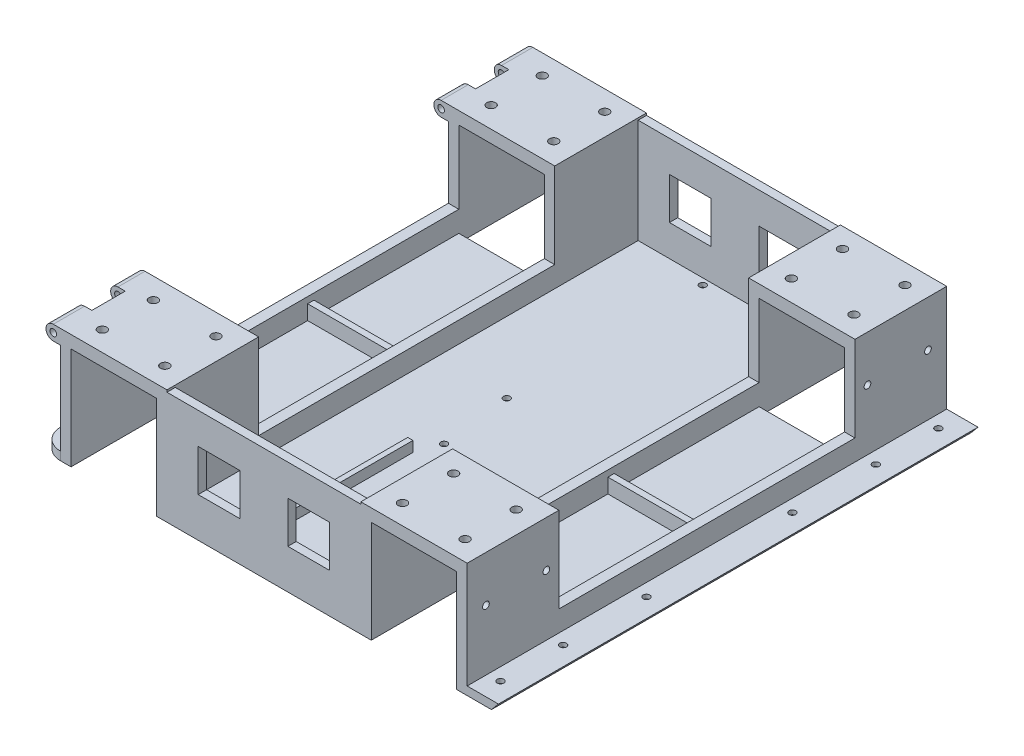
SolidWorks part; units mm, degrees
ref_plane "前视基准面" through (0, 0, 0) normal (0, 0, 1) x (1, 0, 0)
ref_plane "上视基准面" through (0, 0, 0) normal (0, 1, 0) x (1, 0, 0)
ref_plane "右视基准面" through (0, 0, 0) normal (1, 0, 0) x (0, 0, -1)
other "Configuration Table"
sketch "草图1" plane through (0, 0, 0) normal (0, 1, 0) x (1, 0, 0)
  line L0 (-110, 0) -> (110, 0) construction
  line L1 (110, -115) -> (-110, -115)
  line L2 (110, -115) -> (110, 115)
  line L3 (110, 115) -> (-110, 115)
  line L4 (-110, -115) -> (-110, 115)
  line L5 (110, -115) -> (-110, 115) construction
  line L6 (110, 115) -> (-110, -115) construction
  line L7 (0, 115) -> (0, -115) construction
  point P0 (0, 0)
  dimension "D1" = 220
  dimension "D2" = 230
extrude "凸台-拉伸1" add sketch "草图1" along normal blind 4
sketch "草图2" plane through (0, 4, 0) normal (0, 1, 0) x (1, 0, 0)
  line L1 (-95, 71) -> (-100, 71)
  line L2 (49, 115) -> (90, 115)
  line L3 (49, 115) -> (49, 71)
  line L4 (49, 71) -> (90, 71)
  line L5 (-110, 115) -> (-110, -115)
  line L6 (-110, -115) -> (110, -115)
  line L7 (110, -115) -> (110, 115)
  line L8 (110, 115) -> (-110, 115)
  line L9 (-110, 115) -> (-110, -115)
  line L10 (-110, -115) -> (110, -115)
  line L11 (110, -115) -> (110, 115)
  line L12 (110, 115) -> (-110, 115)
  line L13 (90, 115) -> (90, 71)
  line L14 (-95, 115) -> (-54, 115)
  line L15 (-95, 115) -> (-95, 71)
  line L16 (-95, 71) -> (-54, 71)
  line L17 (-54, 115) -> (-54, 71)
  line L18 (-95, -115) -> (-54, -115)
  line L19 (-95, -115) -> (-95, -71)
  line L20 (-95, -71) -> (-54, -71)
  line L21 (-54, -115) -> (-54, -71)
  line L22 (90, -115) -> (49, -115)
  line L23 (90, -115) -> (90, -71)
  line L24 (90, -71) -> (49, -71)
  line L25 (49, -115) -> (49, -71)
  line L26 (90, -115) -> (95, -115)
  line L27 (90, -115) -> (90, -71)
  line L28 (90, -71) -> (95, -71)
  line L29 (95, -115) -> (95, -71)
  line L30 (49, -115) -> (44, -115)
  line L31 (49, -115) -> (49, -71)
  line L32 (49, -71) -> (44, -71)
  line L33 (44, -115) -> (44, -71)
  line L34 (90, 71) -> (95, 71)
  line L35 (90, 71) -> (90, 115)
  line L36 (90, 115) -> (95, 115)
  line L37 (95, 71) -> (95, 115)
  line L38 (49, 71) -> (44, 71)
  line L39 (49, 71) -> (49, 115)
  line L40 (49, 115) -> (44, 115)
  line L41 (44, 71) -> (44, 115)
  line L42 (-54, 71) -> (-49, 71)
  line L43 (-54, 71) -> (-54, 115)
  line L44 (-54, 115) -> (-49, 115)
  line L45 (-49, 71) -> (-49, 115)
  line L46 (-54, -71) -> (-49, -71)
  line L47 (-54, -71) -> (-54, -115)
  line L48 (-54, -115) -> (-49, -115)
  line L49 (-49, -71) -> (-49, -115)
  line L50 (-95, 71) -> (-95, 115)
  line L51 (-95, 115) -> (-100, 115)
  line L52 (-100, 71) -> (-100, 115)
  line L53 (-95, -71) -> (-100, -71)
  line L54 (-95, -71) -> (-95, -115)
  line L55 (-95, -115) -> (-100, -115)
  line L56 (-100, -71) -> (-100, -115)
  line M26 (-110, -115) -> (110, -115)
  line M28 (110, 115) -> (-110, 115)
  dimension "D2" = 44
  dimension "D3" = 41
  dimension "D4" = 44
  dimension "D5" = 41
  dimension "D6" = 41
  dimension "D7" = 44
  dimension "D8" = 44
  dimension "D9" = 41
  dimension "D10" = 15
  dimension "D11" = 15
  dimension "D12" = 20
  dimension "D13" = 20
  dimension "D14" = 5
  dimension "D15" = 5
  dimension "D16" = 5
  dimension "D17" = 5
  dimension "D18" = 5
  dimension "D19" = 5
  dimension "D20" = 5
  dimension "D21" = 5
  dimension "D1" = 0
extrude "凸台-拉伸2" add sketch "草图2" along normal blind 45 contours L53 L56 L10 L19 | L49 L46 L21 M26 | L33 L10 L25 L32 | L29 L28 L23 M26 | L34 L37 L12 L13 | L41 L38 L3 M28 | L42 L45 L17 M28 | L52 L1 L15 M28 region at (-97.5, 4, -93) region at (-51.5, 4, -93) region at (46.5, 4, -93) region at (-97.5, 4, 93) region at (92.5, 4, -93) region at (-51.5, 4, 93) region at (46.5, 4, 93) region at (92.5, 4, 93)
extrude "切除-拉伸1" cut sketch "草图2<3>" against normal up to surface (4 mm away) contours L10 L21 L20 L19 | L25 L10 L23 L24 | L17 L12 L15 L16 | L13 L3 L4 M28 region at (-74.5, 4, -93) region at (69.5, 4, -93) region at (-74.5, 4, 93) region at (69.5, 4, 93) up to face at (0, 0, 0)
sketch "草图2<3>" plane through (0, 4, 0) normal (0, 1, 0) x (1, 0, 0) same geometry as "草图2"
ref_plane "基准面1" through (0, 49, 0) normal (0, 1, 0) x (1, 0, 0)
sketch "草图3" plane through (0, 49, 0) normal (0, 1, 0) x (1, 0, 0)
  line L0 (-100, -115) -> (59, -115)
  line L1 (-168, -115) -> (95, -115)
  line L2 (-100, 115) -> (59, 115)
  line L3 (-170, 115) -> (95, 115)
  line L31 (95, -115) -> (110, -115)
  line L32 (110, -115) -> (110, 115)
  line L33 (110, 115) -> (95, 115)
  line L35 (49, -71) -> (90, -71)
  line L36 (49, -71) -> (90, -71)
  line L37 (90, -71) -> (95, -71)
  line L38 (90, -71) -> (95, -71)
  line L39 (95, -71) -> (95, -115)
  line L40 (95, -71) -> (95, -115)
  line L41 (95, 115) -> (95, 71)
  line L42 (95, 115) -> (95, 71)
  line L43 (-95, 71) -> (-100, 71)
  line L44 (-100, 71) -> (-100, 115)
  line L45 (95, 71) -> (90, 71)
  line L46 (-110, 115) -> (-110, -115)
  line L47 (95, 71) -> (90, 71)
  line L48 (-100, -115) -> (-100, -71)
  line L49 (-100, -71) -> (-95, -71)
  line L50 (90, 71) -> (49, 71)
  line L51 (90, 71) -> (49, 71)
  line L52 (49, 71) -> (44, 71)
  line L53 (49, 71) -> (44, 71)
  line L54 (44, 71) -> (44, 115)
  line L55 (44, 71) -> (44, 115)
  line L59 (95, -115) -> (110, -115)
  line L60 (110, -115) -> (110, 115)
  line L61 (110, 115) -> (95, 115)
  line L71 (-95, 71) -> (-100, 71)
  line L72 (-100, 71) -> (-100, 115)
  line L74 (-110, 115) -> (-110, -115)
  line L76 (-100, -115) -> (-100, -71)
  line L77 (-100, -71) -> (-95, -71)
  line L84 (44, 115) -> (-49, 115)
  line L85 (44, 115) -> (-49, 115)
  line L86 (-49, 115) -> (-49, 71)
  line L87 (-49, 115) -> (-49, 71)
  line L88 (-49, 71) -> (-54, 71)
  line L89 (-49, 71) -> (-54, 71)
  line L90 (-54, 71) -> (-95, 71)
  line L91 (-54, 71) -> (-95, 71)
  line L92 (-100, 115) -> (-110, 115)
  line L93 (-100, 115) -> (-110, 115)
  line L94 (-110, -115) -> (-100, -115)
  line L95 (-110, -115) -> (-100, -115)
  line L96 (-95, -71) -> (-54, -71)
  line L97 (-95, -71) -> (-54, -71)
  line L98 (-54, -71) -> (-49, -71)
  line L99 (-54, -71) -> (-49, -71)
  line L100 (-49, -71) -> (-49, -115)
  line L101 (-49, -71) -> (-49, -115)
  line L102 (-49, -115) -> (44, -115)
  line L103 (-49, -115) -> (44, -115)
  line L104 (44, -115) -> (44, -71)
  line L105 (44, -115) -> (44, -71)
  line L106 (44, -71) -> (49, -71)
  line L107 (44, -71) -> (49, -71)
  dimension "D1" = 0
extrude "凸台-拉伸3" add sketch "草图3" along normal blind 6 contours L101 L99 L97 L77 L76 L0 | L72 L71 L91 L89 L87 L2 | L55 L53 L51 L47 L42 L3 | L107 L105 L1 L40 L38 L36 region at (-74.5, 49, 93) region at (69.5, 49, 93) region at (-74.5, 49, -93) region at (69.5, 49, -93)
sketch "草图4" plane through (0, 49, 0) normal (0, -1, 0) x (1, 0, 0)
  line L0 (69.5, -115) -> (69.5, -71) construction
  line L1 (-74.5, -115) -> (-74.5, -71) construction
  line L2 (110, 115) -> (110, -115) construction
  line L3 (110, 115) -> (110, -115) construction
  line L4 (49, -115) -> (90, -115)
  line L5 (90, -115) -> (90, -71)
  line L6 (90, -71) -> (49, -71)
  line L7 (49, -71) -> (49, -115)
  line L8 (49, -115) -> (90, -115)
  line L9 (90, -115) -> (90, -71)
  line L10 (90, -71) -> (49, -71)
  line L11 (49, -71) -> (49, -115)
  line L12 (-110, -115) -> (-110, 115) construction
  line L13 (-95, -71) -> (-95, -115)
  line L14 (-95, -115) -> (-54, -115)
  line L15 (-54, -115) -> (-54, -71)
  line L16 (-54, -71) -> (-95, -71)
  line L17 (-95, -71) -> (-95, -115)
  line L18 (-95, -115) -> (-54, -115)
  line L19 (-54, -115) -> (-54, -71)
  line L20 (-54, -71) -> (-95, -71)
  line L21 (-110, -115) -> (-110, 115) construction
  line L22 (110, 0) -> (-110, 0) construction
  line L23 (-74.5, 115) -> (-74.5, 71) construction
  line L24 (-54, 71) -> (-95, 71)
  line L25 (-54, 115) -> (-54, 71)
  line L26 (-95, 115) -> (-54, 115)
  line L27 (-95, 71) -> (-95, 115)
  line L28 (69.5, 115) -> (69.5, 71) construction
  line L29 (49, 71) -> (49, 115)
  line L30 (90, 71) -> (49, 71)
  line L31 (90, 115) -> (90, 71)
  line L32 (49, 115) -> (90, 115)
  circle A0 centre (84.5, -105.5) radius 2.1
  circle A1 centre (54.5, -105.5) radius 2.1
  circle A2 centre (54.5, -81) radius 2.1
  circle A3 centre (84.5, -81) radius 2.1
  circle A4 centre (-59.5, -105.5) radius 2.1
  circle A5 centre (-89.5, -105.5) radius 2.1
  circle A6 centre (-59.5, -81) radius 2.1
  circle A7 centre (-89.5, -81) radius 2.1
  circle A8 centre (-89.5, 81) radius 2.1
  circle A9 centre (-59.5, 81) radius 2.1
  circle A10 centre (-89.5, 105.5) radius 2.1
  circle A11 centre (-59.5, 105.5) radius 2.1
  circle A12 centre (84.5, 81) radius 2.1
  circle A13 centre (54.5, 81) radius 2.1
  circle A14 centre (54.5, 105.5) radius 2.1
  circle A15 centre (84.5, 105.5) radius 2.1
  dimension "D4" = 0
  dimension "D5" = 4.2
  dimension "D6" = 4.2
  dimension "D7" = 4.2
  dimension "D9" = 4.2
  dimension "D10" = 4.2
  dimension "D2" = 24.5
  dimension "D3" = 30
  dimension "D8" = 9.5
  dimension "D11" = 30
  dimension "D12" = 24.5
  dimension "D13" = 9.5
  dimension "D1" = 0
extrude "切除-拉伸2" cut sketch "草图4" against normal up to surface (6 mm away) contours A15 | A12 | A14 | A13 | A11 | A9 | A10 | A8 | A7 | A5 | A4 | A6 | A2 | A1 | A0 | A3 region at (84.5, 49, -105.5) region at (54.5, 49, -105.5) region at (54.5, 49, -81) region at (84.5, 49, -81) region at (-59.5, 49, -105.5) region at (-89.5, 49, -105.5) region at (-59.5, 49, -81) region at (-89.5, 49, -81) region at (-89.5, 49, 81) region at (-59.5, 49, 81) region at (-89.5, 49, 105.5) region at (-59.5, 49, 105.5) region at (84.5, 49, 81) region at (54.5, 49, 81) region at (54.5, 49, 105.5) region at (84.5, 49, 105.5) up to face at (69.5, 55, -93)
sketch "草图10" plane through (0, 4, 0) normal (0, 1, 0) x (1, 0, 0)
  line L0 (44, -115) -> (44, -71) construction
  line L1 (-49, -115) -> (44, -115)
  line L2 (-49, -115) -> (-49, -111)
  line L3 (-49, -111) -> (44, -111)
  line L4 (44, -115) -> (44, -111)
  line L5 (44, 71) -> (44, 115) construction
  line L6 (-49, 115) -> (44, 115)
  line L7 (-49, 115) -> (-49, 111)
  line L8 (-49, 111) -> (44, 111)
  line L9 (44, 115) -> (44, 111)
  dimension "D1" = 4
  dimension "D2" = 4
extrude "凸台-拉伸8" add sketch "草图10" along normal blind 50
sketch "草图11" plane through (0, 4, 0) normal (0, 1, 0) x (1, 0, 0)
  line L0 (-95, -71) -> (-100, -71) construction
  line L1 (-49, 71) -> (-54, 71)
  line L2 (-49, 71) -> (-49, -71)
  line L3 (-49, -71) -> (-54, -71)
  line L4 (-54, 71) -> (-54, -71)
  line L5 (90, 71) -> (95, 71)
  line L6 (90, 71) -> (90, -71)
  line L7 (90, -71) -> (95, -71)
  line L8 (95, 71) -> (95, -71)
  line L9 (-95, 71) -> (-100, 71)
  line L10 (-95, 71) -> (-95, -71)
  line L11 (-95, -71) -> (-100, -71)
  line L12 (-100, 71) -> (-100, -71)
  line L14 (49, 71) -> (44, 71)
  line L15 (49, 71) -> (49, -71)
  line L16 (49, -71) -> (44, -71)
  line L17 (44, 71) -> (44, -71)
  dimension "D1" = 5
extrude "凸台-拉伸9" add sketch "草图11" along normal blind 10
sketch "草图13" plane through (0, 4, 0) normal (0, 1, 0) x (1, 0, 0)
  line L0 (-95, 0) -> (-51.7865, 0)
  line L1 (90, 0) -> (49, 0)
  line L2 (-51.7865, -1.5) -> (-95, -1.5)
  line L3 (-51.7865, -1.5) -> (-51.7865, 1.5)
  line L4 (-54, 71) -> (-95, 71)
  line L5 (-95, 71) -> (-95, -71)
  line L6 (-95, -71) -> (-54, -71)
  line L8 (-54, 71) -> (-95, 71)
  line L10 (-95, -71) -> (-54, -71)
  line L12 (-51.7865, 1.5) -> (-95, 1.5)
  line L13 (-95, -1.5) -> (-95, 1.5)
  line L14 (-51.7865, -1.5) -> (-95, 1.5) construction
  line L15 (-51.7865, 1.5) -> (-95, -1.5) construction
  line L17 (49, -1.5) -> (90, -1.5)
  line L18 (49, -1.5) -> (49, 1.5)
  line L19 (-95, 71) -> (-95, -71)
  line L20 (-54, -71) -> (-54, 71)
  line L21 (-54, -71) -> (-54, 71)
  line L22 (90, 71) -> (49, 71)
  line L23 (49, 71) -> (49, -71)
  line L24 (49, -71) -> (90, -71)
  line L25 (90, -71) -> (90, 71)
  line L26 (90, 71) -> (49, 71)
  line L27 (49, 71) -> (49, -71)
  line L28 (49, -71) -> (90, -71)
  line L29 (90, -71) -> (90, 71)
  line L30 (49, 1.5) -> (90, 1.5)
  line L31 (90, -1.5) -> (90, 1.5)
  line L32 (49, -1.5) -> (90, 1.5) construction
  line L33 (49, 1.5) -> (90, -1.5) construction
  point P6 (-73.3932, 0)
  point P11 (69.5, 0)
  line M8 (-95, 71) -> (-95, -71)
  line M10 (-54, -71) -> (-54, 71)
  dimension "D2" = 3
  dimension "D4" = 3
  dimension "D1" = 0
  dimension "D3" = 0
extrude "凸台-拉伸11" add sketch "草图13" along normal blind 7 contours L2 L0 M10 M8 | L12 L19 L0 M10 | L30 L18 L1 L29 | L17 L29 L1 L18 region at (-74.5, 4, -0.75) region at (-74.5, 4, 0.75) region at (69.5, 4, 0.75) region at (69.5, 4, -0.75)
sketch "草图17" plane through (0, 4, 0) normal (0, 1, 0) x (1, 0, 0)
  line L0 (101, -115) -> (101, -71) construction
  line L1 (133.9214, 0) -> (95, 0) construction
  line L4 (110, 115) -> (95, 115)
  line L5 (95, 115) -> (95, -115)
  line L6 (95, -115) -> (110, -115)
  line L7 (110, -115) -> (110, 115)
  line L9 (95, 115) -> (95, -115)
  line L10 (95, -115) -> (110, -115)
  line L14 (110, -115) -> (110, 115)
  line L15 (110, 115) -> (95, 115)
  circle A2 centre (101, -35) radius 1.6
  circle A3 centre (101, -75) radius 1.6
  circle A4 centre (101, -105) radius 1.6
  circle A5 centre (101, 35) radius 1.6
  circle A6 centre (101, 75) radius 1.6
  circle A7 centre (101, 105) radius 1.6
  dimension "D3" = 35
  dimension "D4" = 3.2
  dimension "D5" = 3.2
  dimension "D6" = 3.2
  dimension "D2" = 6
  dimension "D7" = 75
  dimension "D8" = 105
  dimension "D1" = 0
extrude "切除-拉伸7" cut sketch "草图17" against normal up to surface (4 mm away) contours A4 | A3 | A2 | A5 | A6 | A7 region at (101, 4, 35) region at (101, 4, 75) region at (101, 4, 105) region at (101, 4, -35) region at (101, 4, -75) region at (101, 4, -105) up to face at (-2, 0, 0)
chamfer "倒角3" distance 4 angle 40 1 edges at (110, 0, 0) first distance on face at (110, 2, 0)
sketch "草图21" plane through (0, 0, -111) normal (0, 0, 1) x (1, 0, 0)
  line L1 (-34, 39) -> (-14, 39)
  line L2 (-34, 39) -> (-34, 19)
  line L3 (-34, 19) -> (-14, 19)
  line L4 (-49, 4) -> (44, 4)
  line L5 (44, 4) -> (44, 54)
  line L6 (44, 54) -> (-49, 54)
  line L7 (-49, 54) -> (-49, 4)
  line L8 (-49, 4) -> (44, 4)
  line L9 (44, 4) -> (44, 54)
  line L10 (44, 54) -> (-49, 54)
  line L11 (-49, 54) -> (-49, 4)
  line L12 (-14, 39) -> (-14, 19)
  line L13 (9, 39) -> (29, 39)
  line L14 (9, 39) -> (9, 19)
  line L15 (9, 19) -> (29, 19)
  line L16 (29, 39) -> (29, 19)
  dimension "D2" = 20
  dimension "D3" = 20
  dimension "D4" = 20
  dimension "D5" = 20
  dimension "D6" = 15
  dimension "D7" = 35
  dimension "D8" = 35
  dimension "D10" = 15
  dimension "D1" = 0
extrude "切除-拉伸11" cut sketch "草图21" against normal up to surface (4 mm away) and the other way through all contours L16 L13 L14 L15 | L12 L1 L2 L3 region at (-24, 29, -111) region at (19, 29, -111) up to face at (-2.1678, 27, -115)
sketch "草图23" plane through (0, 0, -71) normal (0, 0, 1) x (1, 0, 0)
  line L0 (-103.5, 55) -> (-100, 55)
  line L1 (-103.5, 48) -> (-100, 48)
  line L2 (-100, 48) -> (-100, 55)
  line L10 (-100, 55) -> (-100, 14)
  line L12 (-100, 55) -> (-100, 14)
  line L13 (-95, 49) -> (-54, 49)
  line L15 (-100, 14) -> (-95, 14)
  line L17 (-49, 55) -> (-100, 55)
  line L19 (-100, 14) -> (-95, 14)
  line L23 (-95, 49) -> (-54, 49)
  line L27 (-49, 55) -> (-100, 55)
  line L31 (-95, 14) -> (-95, 49)
  line L33 (-95, 14) -> (-95, 49)
  line L34 (-54, 49) -> (-54, 14)
  line L35 (-54, 49) -> (-54, 14)
  line L36 (-54, 14) -> (-49, 14)
  line L37 (-54, 14) -> (-49, 14)
  line L38 (-49, 14) -> (-49, 55)
  line L39 (-49, 14) -> (-49, 55)
  arc A0 (-103.5, 55) -> (-103.5, 48) centre (-103.5, 51.5) ccw
  circle A1 centre (-103.5, 51.5) radius 1.6
  line M19 (-100, 55) -> (-100, 14)
  dimension "D2" = 7
  dimension "D3" = 3.2
  dimension "D1" = 0
extrude "凸台-拉伸13" add sketch "草图23" against normal up to surface (44 mm away) contours L0 A0 L1 A1 M19 region at (-101.75, 54.901, -71) up to face at (-24, 29, -115)
extrude "切除-拉伸13" cut sketch "草图23<4>" against normal blind 16 from offset 13 contours L0 A0 L1 A1 M19 region at (-101.75, 54.901, -71) offset against normal yes
sketch "草图23<4>" plane through (0, 0, -71) normal (0, 0, 1) x (1, 0, 0) same geometry as "草图23"
extrude "凸台-拉伸14" add sketch "草图23<5>" along normal up to surface (186 mm away) from surface contours L0 A0 L1 A1 M19 region at (-101.75, 54.901, -71) up to face at (-24, 29, 115) starting at face at (-74.5, 33, 71)
sketch "草图23<5>" plane through (0, 0, -71) normal (0, 0, 1) x (1, 0, 0) same geometry as "草图23"
sketch "草图24" plane through (0, 4, 0) normal (0, 1, 0) x (1, 0, 0)
  line L1 (44, -111) -> (-14, -111)
  line L2 (44, -111) -> (44, -26)
  line L3 (44, -26) -> (-14, -26)
  line L4 (-49, -111) -> (44, -111)
  line L5 (44, -111) -> (44, 111)
  line L6 (44, 111) -> (-49, 111)
  line L7 (-49, 111) -> (-49, -111)
  line L8 (-49, -111) -> (44, -111)
  line L9 (44, -111) -> (44, 111)
  line L10 (44, 111) -> (-49, 111)
  line L11 (-49, 111) -> (-49, -111)
  line L12 (-14, -111) -> (-14, -26)
  line L13 (-15, -111) -> (-17.5, -111)
  line L14 (-15, -111) -> (-15, -31)
  line L15 (-15, -31) -> (-17.5, -31)
  line L16 (-17.5, -111) -> (-17.5, -31)
  dimension "D2" = 85
  dimension "D3" = 58
  dimension "D4" = 2.5
  dimension "D5" = 1
  dimension "D1" = 0
extrude "凸台-拉伸15" add sketch "草图24" along normal blind 5 contours L16 L8 L14 L15 region at (-16.25, 4, 71)
sketch "草图25" plane through (0, 4, 0) normal (0, 1, 0) x (1, 0, 0)
  line L8 (-17.5, -111) -> (-17.5, -31)
  line L9 (-17.5, -31) -> (-15, -31)
  line L10 (-15, -31) -> (-15, -111)
  line L11 (-15, -111) -> (44, -111)
  line L12 (44, -111) -> (44, 111)
  line L13 (44, 111) -> (-49, 111)
  line L14 (-49, 111) -> (-49, -111)
  line L15 (-49, -111) -> (-17.5, -111)
  line L16 (-17.5, -111) -> (-17.5, -31)
  line L17 (-17.5, -31) -> (-15, -31)
  line L18 (-15, -31) -> (-15, -111)
  line L19 (-15, -111) -> (44, -111)
  line L20 (44, -111) -> (44, 111)
  line L21 (44, 111) -> (-49, 111)
  line L22 (-49, 111) -> (-49, -111)
  line L23 (-49, -111) -> (-17.5, -111)
  circle A0 centre (40.9, -20) radius 1.6
  circle A1 centre (-11.1, -20) radius 1.6
  dimension "D2" = 3.2
  dimension "D3" = 3.2
  dimension "D1" = 52
  dimension "D5" = 91
  dimension "D6" = 91
  dimension "D7" = 3.1
  dimension "D4" = 0
extrude "切除-拉伸15" cut sketch "草图25" against normal up to surface (4 mm away) contours A0 | A1 region at (40.9, 4, 20) region at (-11.1, 4, 20) up to face at (101, 0, 106.6)
mirror "镜向6" about plane through (0, 0, 0) normal (0, 0, 1) of "切除-拉伸13"
fillet "圆角1" radius 10 2 edges at (-110, 2, 115) (-110, 2, -115)
sketch "草图26" plane through (0, 4, 0) normal (0, 1, 0) x (1, 0, 0)
  line L0 (13, 11) -> (13, 111) construction
  line L1 (44, 111) -> (-18, 111)
  line L2 (44, 111) -> (44, 11)
  line L3 (44, 11) -> (-18, 11)
  line L4 (-18, 111) -> (-18, 11)
  line L5 (-18, 61) -> (44, 61) construction
  line L8 (-17.5, -111) -> (-17.5, -31)
  line L9 (-17.5, -31) -> (-15, -31)
  line L10 (-15, -31) -> (-15, -111)
  line L11 (-15, -111) -> (44, -111)
  line L12 (44, -111) -> (44, 111)
  line L13 (44, 111) -> (-49, 111)
  line L14 (-49, 111) -> (-49, -111)
  line L15 (-49, -111) -> (-17.5, -111)
  line L16 (-17.5, -111) -> (-17.5, -31)
  line L17 (-17.5, -31) -> (-15, -31)
  line L18 (-15, -31) -> (-15, -111)
  line L19 (-15, -111) -> (44, -111)
  line L20 (44, -111) -> (44, 111)
  line L21 (44, 111) -> (-49, 111)
  line L22 (-49, 111) -> (-49, -111)
  line L23 (-49, -111) -> (-17.5, -111)
  circle A0 centre (41, 14) radius 1.6
  circle A1 centre (-15, 14) radius 1.6
  circle A2 centre (41, 108) radius 1.6
  circle A3 centre (-15, 108) radius 1.6
  dimension "D6" = 3.2
  dimension "D2" = 100
  dimension "D3" = 62
  dimension "D4" = 56
  dimension "D5" = 94
  dimension "D1" = 0
extrude "切除-拉伸16" cut sketch "草图26" against normal up to surface (4 mm away) contours A2 | A0 | A1 | A3 region at (41, 4, -14) region at (-15, 4, -14) region at (41, 4, -108) region at (-15, 4, -108) up to face at (40.9, 0, 21.6)
sketch "草图27" plane through (0, 0, 0) normal (0, -1, 0) x (1, 0, 0)
  circle A0 centre (101, 105) radius 3
  circle A1 centre (101, 75) radius 3
  circle A2 centre (101, 35) radius 3
  circle A3 centre (101, -35) radius 3
  circle A4 centre (101, -75) radius 3
  circle A5 centre (101, -105) radius 3
  circle A6 centre (40.9, 20) radius 3
  circle A7 centre (41, -14) radius 3
  circle A8 centre (41, -108) radius 3
  circle A9 centre (-11.1, 20) radius 3
  circle A10 centre (-15, -14) radius 3
  circle A11 centre (-15, -108) radius 3
  dimension "D1" = 6
  dimension "D2" = 6
  dimension "D3" = 6
  dimension "D4" = 6
  dimension "D5" = 6
  dimension "D6" = 6
  dimension "D7" = 6
  dimension "D8" = 6
  dimension "D9" = 6
  dimension "D10" = 6
  dimension "D11" = 6
  dimension "D12" = 6
extrude "切除-拉伸17" cut sketch "草图27" against normal blind 2
sketch "草图28" plane through (95, 0, 0) normal (1, 0, 0) x (0, 0, -1)
  line L0 (-115, 33) -> (115, 33) construction
  line L1 (-115, 55) -> (-115, 4) construction
  line L2 (115, 55) -> (115, 4) construction
  line L3 (-115, 4) -> (115, 4) construction
  circle A0 centre (-106, 33) radius 1.6
  circle A1 centre (-77, 33) radius 1.6
  circle A2 centre (77, 33) radius 1.6
  circle A3 centre (106, 33) radius 1.6
  dimension "D2" = 3.2
  dimension "D3" = 3.2
  dimension "D4" = 3.2
  dimension "D5" = 3.2
  dimension "D1" = 29
  dimension "D6" = 9
  dimension "D7" = 29
  dimension "D8" = 9
  dimension "D9" = 29
extrude "切除-拉伸18" cut sketch "草图28" against normal up to next
